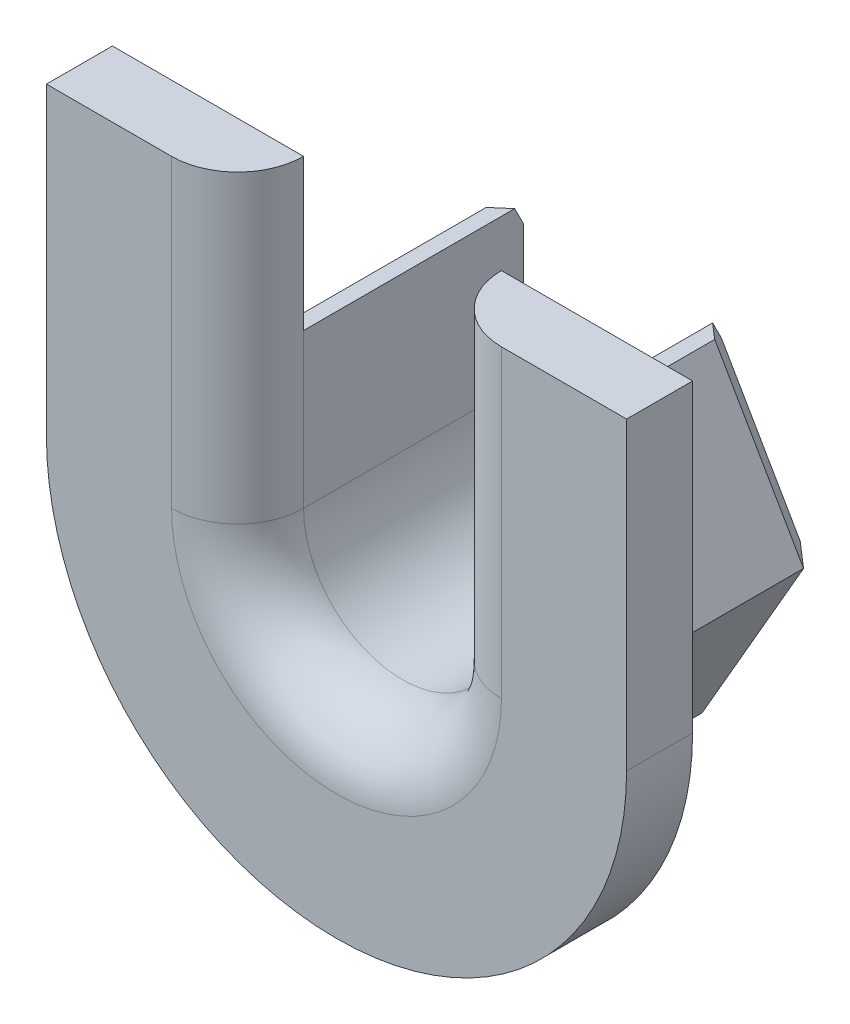
SolidWorks part; units mm, degrees
ref_plane "Front Plane" through (0, 0, 0) normal (0, 0, 1) x (1, 0, 0)
ref_plane "Top Plane" through (0, 0, 0) normal (0, 1, 0) x (1, 0, 0)
ref_plane "Right Plane" through (0, 0, 0) normal (1, 0, 0) x (0, 0, -1)
sketch "Sketch1" plane through (0, 0, 0) normal (0, 0, 1) x (1, 0, 0)
  line L0 (9.73, -24.18) -> (9.73, -20.18)
  line L1 (5.23, -24.18) -> (5.23, -20.18)
  line L12 (2.8612, -24.18) -> (5.1706, -28.18)
  line L13 (5.1706, -28.18) -> (9.7894, -28.18)
  line L14 (9.7894, -28.18) -> (12.0988, -24.18)
  line L15 (12.0988, -24.18) -> (9.7894, -20.18)
  line L16 (9.7894, -20.18) -> (5.1706, -20.18)
  line L17 (5.1706, -20.18) -> (2.8612, -24.18)
  line L18 (2.8612, -24.18) -> (5.1706, -28.18)
  line L19 (5.1706, -28.18) -> (9.7894, -28.18)
  line L20 (9.7894, -28.18) -> (12.0988, -24.18)
  line L21 (12.0988, -24.18) -> (9.7894, -20.18)
  line L22 (9.7894, -20.18) -> (5.1706, -20.18)
  line L23 (5.1706, -20.18) -> (2.8612, -24.18)
  line L32 (4.8819, -20.68) -> (10.0781, -20.68)
  circle A2 centre (7.48, -24.18) radius 2.25
  circle A3 centre (7.48, -24.18) radius 2.25
  dimension "D3" = 0.5
  dimension "D1" = 0.25
  dimension "D2" = 0.25
extrude "Boss-Extrude1" add sketch "Sketch1" against normal blind 5 contours A3 L19 L20 L21 L22 L23 L18 region at (9.849, -22.43, 0)
sketch "Sketch2" plane through (0, 0, 0) normal (0, 0, 1) x (1, 0, 0)
  line L0 (0.885, -19.25) -> (0.885, -17.25)
  line L3 (5.23, -24.18) -> (5.23, -20.68) construction
  line L4 (9.73, -24.18) -> (9.73, -20.68) construction
  line L5 (5.23, -24.18) -> (5.23, -20.68)
  line L6 (9.73, -24.18) -> (9.73, -20.68)
  line L7 (-14.075, -19.25) -> (0.885, -19.25)
  line L8 (0.885, -19.25) -> (0.885, -24.18)
  line L9 (14.075, -24.18) -> (14.075, -17.25)
  line L10 (14.075, -17.25) -> (10.575, -17.25)
  line L11 (10.575, -17.25) -> (-10.575, -17.25)
  line L12 (-10.575, -17.25) -> (-14.075, -17.25)
  line L13 (-14.075, -17.25) -> (-14.075, -19.25)
  line L14 (-14.075, -19.25) -> (0.885, -19.25)
  line L15 (0.885, -19.25) -> (0.885, -24.18)
  line L16 (14.075, -24.18) -> (14.075, -17.25)
  line L17 (14.075, -17.25) -> (10.575, -17.25)
  line L18 (10.575, -17.25) -> (-10.575, -17.25)
  line L19 (-10.575, -17.25) -> (-14.075, -17.25)
  line L20 (-14.075, -17.25) -> (-14.075, -19.25)
  line L21 (9.73, -20.68) -> (9.73, -17.25)
  line L22 (5.23, -20.68) -> (5.23, -17.25)
  arc A0 (5.23, -24.18) -> (9.73, -24.18) centre (7.48, -24.18) ccw construction
  arc A1 (0.885, -24.18) -> (14.075, -24.18) centre (7.48, -24.18) ccw
  arc A2 (0.885, -24.18) -> (14.075, -24.18) centre (7.48, -24.18) ccw
  arc A3 (5.23, -24.18) -> (9.73, -24.18) centre (7.48, -24.18) ccw
  arc M9 (9.73, -24.18) -> (5.23, -24.18) centre (7.48, -24.18) cw
  line M11 (5.1706, -28.18) -> (9.7894, -28.18)
  line M12 (9.7894, -28.18) -> (12.0988, -24.18)
  line M13 (12.0988, -24.18) -> (10.0781, -20.68)
  line M15 (4.8819, -20.68) -> (2.8612, -24.18)
  line M16 (2.8612, -24.18) -> (5.1706, -28.18)
  line M17 (5.1706, -28.18) -> (9.7894, -28.18)
  dimension "D1" = 0
extrude "Boss-Extrude2" add sketch "Sketch2" along normal blind 1.5 contours L15 A2 L16 L17 L18 L0 M17 M16 M15 M13 M12 M11 | M9 M11 M12 M13 M15 M16 M17 region at (1.0739, -18.25, 0)
fillet "Fillet1" radius 1.5 3 edges at (9.73, -20.715, 1.5) (5.23, -20.715, 1.5) (7.48, -26.43, 1.5)
chamfer "Chamfer1" distance 0.5 angle 45 5 edges at (3.8716, -22.43, -5) (4.0159, -26.18, -5) (7.48, -28.18, -5) (10.9441, -26.18, -5) (11.0884, -22.43, -5)
